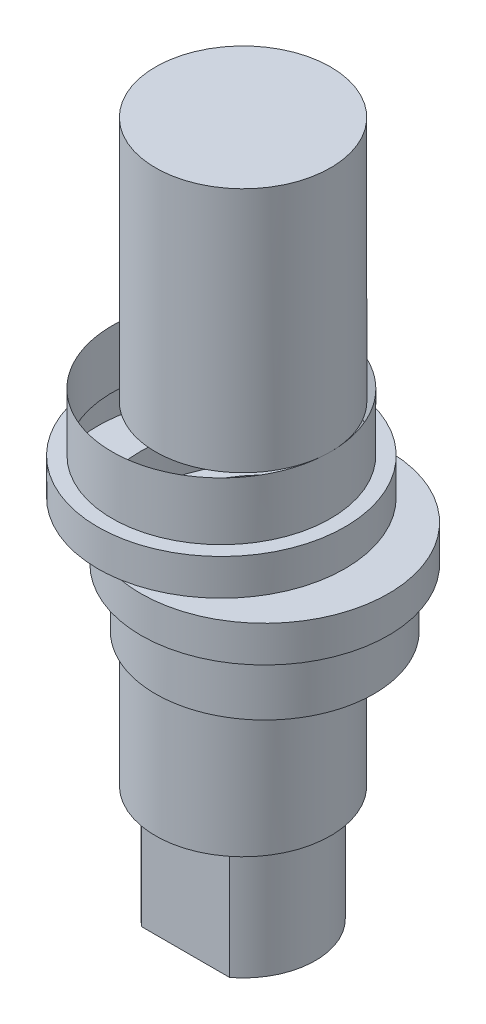
SolidWorks part; units mm, degrees
ref_plane "Front Plane" through (0, 0, 0) normal (0, 0, 1) x (1, 0, 0)
ref_plane "Top Plane" through (0, 0, 0) normal (0, 1, 0) x (1, 0, 0)
ref_plane "Right Plane" through (0, 0, 0) normal (1, 0, 0) x (0, 0, -1)
sketch "Sketch1" plane through (0, 0, 0) normal (0, 0, 1) x (1, 0, 0)
  line L0 (0, 0) -> (0, 40)
  line L1 (-1.5, 0) -> (-1.5, 40) construction
  line L2 (-1.5, 40) -> (1.5, 40) construction
  line L3 (-1.5, 0) -> (1.5, 0) construction
  line L4 (1.5, 0) -> (1.5, 40) construction
  line L6 (-6.05, 14) -> (9.05, 14)
  line L7 (-6.05, 14) -> (-6.05, 10)
  line L8 (-6.05, 10) -> (9.05, 10)
  line L9 (9.05, 14) -> (9.05, 10)
  line L10 (-6.05, 14) -> (9.05, 10) construction
  line L11 (-6.05, 10) -> (9.05, 14) construction
  line L12 (-9.05, 23) -> (6.05, 23)
  line L13 (-9.05, 23) -> (-9.05, 19)
  line L14 (-9.05, 19) -> (6.05, 19)
  line L15 (6.05, 23) -> (6.05, 19)
  line L16 (-9.05, 23) -> (6.05, 19) construction
  line L17 (-9.05, 19) -> (6.05, 23) construction
  line L20 (-6.05, 0) -> (6.05, 0)
  line L21 (-6.05, 0) -> (-6.05, 40)
  line L22 (-6.05, 40) -> (6.05, 40)
  line L23 (6.05, 0) -> (6.05, 40)
  line L24 (-6.05, 0) -> (6.05, 40) construction
  line L25 (-6.05, 40) -> (6.05, 0) construction
  point P7 (1.5, 12)
  point P12 (-1.5, 21)
  point P19 (0, 20)
  point P24 (0, 20)
  dimension "D1" = 3
  dimension "D2" = 40
  dimension "D3" = 15.1
  dimension "D4" = 4
  dimension "D5" = 5
  dimension "D6" = 12
revolve "Revolve4" add sketch "Sketch1" angle 360 about L0 region at (-3.025, 5, 0) region at (-3.025, 12, 0) region at (-3.025, 16.5, 0) region at (-3.025, 21, 0) region at (-3.025, 31.5, 0)
revolve "Revolve5" add sketch "Sketch1<5>" angle 360 about L1 region at (-7.55, 21, 0)
sketch "Sketch1<5>" plane through (0, 0, 0) normal (0, 0, 1) x (1, 0, 0) same geometry as "Sketch1"
revolve "Revolve6" add sketch "Sketch1<6>" angle 360 about L4 region at (7.55, 12, 0)
sketch "Sketch1<6>" plane through (0, 0, 0) normal (0, 0, 1) x (1, 0, 0) same geometry as "Sketch1"
sketch "Sketch2" plane through (0, 0, 0) normal (0, 0, 1) x (1, 0, 0)
  line L2 (0, 19) -> (0, 14) construction
  line L7 (-6.05, 19) -> (6.05, 19) construction
  line L10 (9.05, 14) -> (-6.05, 14) construction
  line L16 (-1.5, 19) -> (-1.5, 14) construction
  line L17 (1.5, 19) -> (1.5, 14) construction
  line L26 (-9.05, 19) -> (6.05, 19) construction
  line L27 (9.05, 14) -> (-6.05, 14) construction
  line L28 (-9.05, 19) -> (6.05, 19) construction
  line L29 (9.05, 10) -> (9.05, 14) construction
  line L30 (-1.5, 19) -> (-10.05, 19)
  line L31 (-1.5, 19) -> (-1.5, 16.5)
  line L32 (-1.5, 16.5) -> (-10.05, 16.5)
  line L33 (-10.05, 19) -> (-10.05, 16.5)
  line L34 (1.5, 16.5) -> (10.05, 16.5)
  line L35 (1.5, 16.5) -> (1.5, 14)
  line L36 (1.5, 14) -> (10.05, 14)
  line L37 (10.05, 16.5) -> (10.05, 14)
  dimension "D1" = 1
revolve "Revolve7" add sketch "Sketch2" angle 360 about L16 region at (-5.775, 17.75, 0)
revolve "Revolve8" add sketch "Sketch2<3>" angle 360 about L17 region at (5.775, 15.25, 0)
sketch "Sketch2<3>" plane through (0, 0, 0) normal (0, 0, 1) x (1, 0, 0) same geometry as "Sketch2"
sketch "Sketch3" plane through (0, 0, 0) normal (0, -1, 0) x (1, 0, 0)
  line L0 (-3.0412, 3.9688) -> (3.0412, 3.9688)
  line L1 (-3.0412, -3.9688) -> (3.0412, -3.9688)
  line L2 (0, -3.9688) -> (0, 0) construction
  line L3 (0, 0) -> (0, 3.9688) construction
  circle A0 centre (0, 0) radius 5
  dimension "D1" = 10
  dimension "D2" = 7.9375
extrude "Boss-Extrude1" add sketch "Sketch3" along normal blind 8 contours L1 A0 L0 region at (0, 0, 0)
sketch "Sketch4" plane through (0, -8, 0) normal (0, -1, 0) x (1, 0, 0)
  circle A0 centre (0, 0) radius 1.55
  dimension "D1" = 3.1
extrude "Cut-Extrude1" cut sketch "Sketch4" against normal up to surface (8 mm away) up to face at (0, 0, 0)
equation "\"Ratio\"= 15"
equation "\"Hull Diameter\"= 3.5in"
equation "\"Fixed Ring Diameter\"= 76"
equation "\"Fixed Pin Diameter\"= 6"
equation "\"Output Ring Diameter\"= 40"
equation "\"Output Pin Diameter\"= 6"
equation "\"Disk Bearing Inner Diameter\"= 9"
equation "\"Disk Bearing Outer Diameter\"= 17"
equation "\"Disk Bearing Height\"= 5"
equation "\"Shaft Bearing Inner Diameter\"= 15"
equation "\"Shaft Bearing Outer Diameter\"= 21"
equation "\"Shaft Bearing Height\"= 4"
equation "\"Eccentricity\"= 1.5"
equation "\"Disk Height\"= 8"
equation "\"Disk Spacing\"= 5"
equation "\"Hull Height\"= 40"
equation "\"Shaft End Bearing Inner Diameter\"= 12"
equation "\"Shaft End Bearing Outer Diameter\"= 18"
equation "\"Shaft End Bearing Height\"= 4"
equation "\"Output Bearing Inner Diameter\"= 55"
equation "\"Output Bearing Outer Diameter\"= 72"
equation "\"Outer Bearing Height\"= 9"
equation "\"D1@Sketch1\"=\"Eccentricity\"*2"
equation "\"D2@Sketch1\"=\"Hull Height\""
equation "\"D3@Sketch1\"=\"Shaft Bearing Inner Diameter\"+0.1"
equation "\"D4@Sketch1\"=\"Shaft Bearing Height\""
equation "\"D5@Sketch1\"=\"Disk Spacing\""
